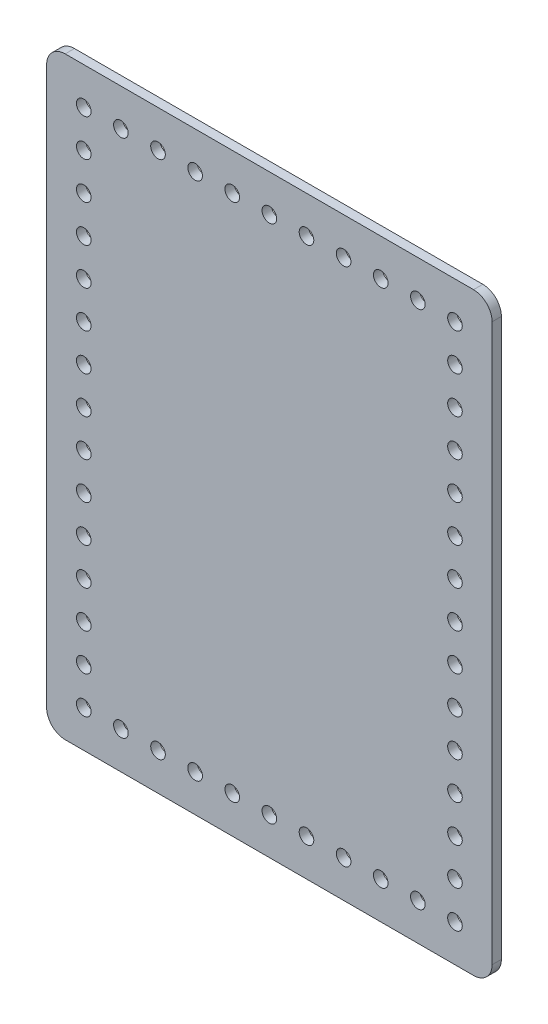
SolidWorks part; units mm, degrees
ref_plane "Front Plane" through (0, 0, 0) normal (0, 0, 1) x (1, 0, 0)
ref_plane "Top Plane" through (0, 0, 0) normal (0, 1, 0) x (1, 0, 0)
ref_plane "Right Plane" through (0, 0, 0) normal (1, 0, 0) x (0, 0, -1)
sketch "Sketch1" plane through (0, 0, 0) normal (0, 0, 1) x (1, 0, 0)
  line L1 (-367.5063, 266.7) -> (-227.8063, 266.7)
  line L2 (-373.8563, 260.35) -> (-373.8563, 69.85)
  line L3 (-367.5063, 63.5) -> (-227.8063, 63.5)
  line L4 (-221.4563, 260.35) -> (-221.4563, 69.85)
  arc A0 (-373.8563, 69.85) -> (-367.5063, 63.5) centre (-367.5063, 69.85) ccw
  arc A1 (-227.8063, 63.5) -> (-221.4563, 69.85) centre (-227.8063, 69.85) ccw
  arc A2 (-227.8063, 266.7) -> (-221.4563, 260.35) centre (-227.8063, 260.35) cw
  arc A3 (-367.5063, 266.7) -> (-373.8563, 260.35) centre (-367.5063, 260.35) ccw
  point P6 (-373.8563, 63.5)
  point P11 (-221.4563, 266.7)
  point P14 (-373.8563, 266.7)
  dimension "D3" = 6.35
  dimension "D1" = 152.4
  dimension "D2" = 203.2
extrude "Boss-Extrude1" add sketch "Sketch1" along normal blind 3.175
sketch "Sketch3" plane through (0, 0, 3.175) normal (0, 0, 1) x (1, 0, 0)
  line L0 (-373.8563, 260.35) -> (-373.8563, 69.85) construction
  line L1 (-227.8063, 266.7) -> (-367.5063, 266.7) construction
  line L2 (-221.4563, 69.85) -> (-221.4563, 260.35) construction
  line L3 (-367.5063, 63.5) -> (-227.8063, 63.5) construction
  circle A0 centre (-234.1563, 254) radius 2.5
  circle A1 centre (-361.1563, 254) radius 2.5
  circle A2 centre (-361.1562, 241.3) radius 2.5
  circle A3 centre (-234.1562, 241.3) radius 2.5
  circle A4 centre (-361.1562, 228.6) radius 2.5
  circle A5 centre (-234.1562, 228.6) radius 2.5
  circle A6 centre (-361.1562, 215.9) radius 2.5
  circle A7 centre (-234.1562, 215.9) radius 2.5
  circle A8 centre (-361.1562, 203.2) radius 2.5
  circle A9 centre (-234.1562, 203.2) radius 2.5
  circle A10 centre (-361.1562, 190.5) radius 2.5
  circle A11 centre (-234.1562, 190.5) radius 2.5
  circle A12 centre (-361.1562, 177.8) radius 2.5
  circle A13 centre (-234.1562, 177.8) radius 2.5
  circle A14 centre (-361.1562, 165.1) radius 2.5
  circle A15 centre (-234.1562, 165.1) radius 2.5
  circle A16 centre (-361.1562, 152.4) radius 2.5
  circle A17 centre (-234.1562, 152.4) radius 2.5
  circle A18 centre (-361.1562, 139.7) radius 2.5
  circle A19 centre (-234.1562, 139.7) radius 2.5
  circle A20 centre (-361.1562, 127) radius 2.5
  circle A21 centre (-234.1562, 127) radius 2.5
  circle A22 centre (-361.1562, 114.3) radius 2.5
  circle A23 centre (-234.1562, 114.3) radius 2.5
  circle A24 centre (-361.1562, 101.6) radius 2.5
  circle A25 centre (-234.1562, 101.6) radius 2.5
  circle A26 centre (-361.1562, 88.9) radius 2.5
  circle A27 centre (-234.1562, 88.9) radius 2.5
  circle A28 centre (-361.1562, 76.2) radius 2.5
  circle A29 centre (-234.1562, 76.2) radius 2.5
  circle A30 centre (-348.4563, 254) radius 2.5
  circle A31 centre (-348.4563, 76.2) radius 2.5
  circle A32 centre (-335.7563, 254) radius 2.5
  circle A33 centre (-335.7563, 76.2) radius 2.5
  circle A34 centre (-323.0563, 254) radius 2.5
  circle A35 centre (-323.0563, 76.2) radius 2.5
  circle A36 centre (-310.3563, 254) radius 2.5
  circle A37 centre (-310.3563, 76.2) radius 2.5
  circle A38 centre (-297.6563, 254) radius 2.5
  circle A39 centre (-297.6563, 76.2) radius 2.5
  circle A40 centre (-284.9563, 254) radius 2.5
  circle A41 centre (-284.9563, 76.2) radius 2.5
  circle A42 centre (-272.2563, 254) radius 2.5
  circle A43 centre (-272.2563, 76.2) radius 2.5
  circle A44 centre (-259.5563, 254) radius 2.5
  circle A45 centre (-259.5563, 76.2) radius 2.5
  circle A46 centre (-246.8563, 254) radius 2.5
  circle A47 centre (-246.8563, 76.2) radius 2.5
  circle A48 centre (-234.1563, 254) radius 2.5
  circle A49 centre (-234.1563, 76.2) radius 2.5
  point P74 (0, 0)
  point P109 (0, 0)
  dimension "D1" = 5
  dimension "D4" = 5
  dimension "D8" = 5
  dimension "D10" = 5
  dimension "D2" = 12.7
  dimension "D3" = 12.7
  dimension "D5" = 12.7
  dimension "D6" = 12.7
  dimension "D9" = 25.4
  dimension "D11" = 12.7
  dimension "D12" = 25.4
  dimension "D13" = 12.7
  dimension "D7" = 15
  dimension "D14" = 10
extrude "Cut-Extrude2" cut sketch "Sketch3" against normal through all contours A1 | A2 | A8 | A10 | A12 | A14 | A16 | A18 | A20 | A26 | A31 | A33 | A28 | A35 | A37 | A39 | A41 | A43 | A45 | A27 | A25 | A23 | A21 | A7 | A5 | A3 | A0 | A46 | A44 | A30 | A32 | A34 | A36 | A40 | A4 | A6 | A22 | A24 | A28 | A47 | A29 | A17 | A19 | A15 | A13 | A11 | A9 | A42 | A38 region at (-234.1563, 254, 3.175) region at (-361.1563, 254, 3.175) region at (-361.1562, 241.3, 3.175) region at (-234.1562, 241.3, 3.175) region at (-234.1562, 228.6, 3.175) region at (-234.1562, 215.9, 3.175) region at (-361.1562, 203.2, 3.175) region at (-361.1562, 190.5, 3.175) region at (-361.1562, 177.8, 3.175) region at (-361.1562, 165.1, 3.175) region at (-361.1562, 152.4, 3.175) region at (-361.1562, 139.7, 3.175) region at (-361.1562, 127, 3.175) region at (-234.1562, 127, 3.175) region at (-234.1562, 114.3, 3.175) region at (-234.1562, 101.6, 3.175) region at (-361.1562, 88.9, 3.175) region at (-234.1562, 88.9, 3.175) region at (-361.1562, 76.2, 3.175) region at (-348.4563, 254, 3.175) region at (-348.4563, 76.2, 3.175) region at (-335.7563, 254, 3.175) region at (-335.7563, 76.2, 3.175) region at (-323.0563, 254, 3.175) region at (-323.0563, 76.2, 3.175) region at (-310.3563, 254, 3.175) region at (-310.3563, 76.2, 3.175) region at (-297.6563, 76.2, 3.175) region at (-284.9563, 254, 3.175) region at (-284.9563, 76.2, 3.175) region at (-272.2563, 76.2, 3.175) region at (-259.5563, 254, 3.175) region at (-259.5563, 76.2, 3.175) region at (-246.8563, 254, 3.175)
